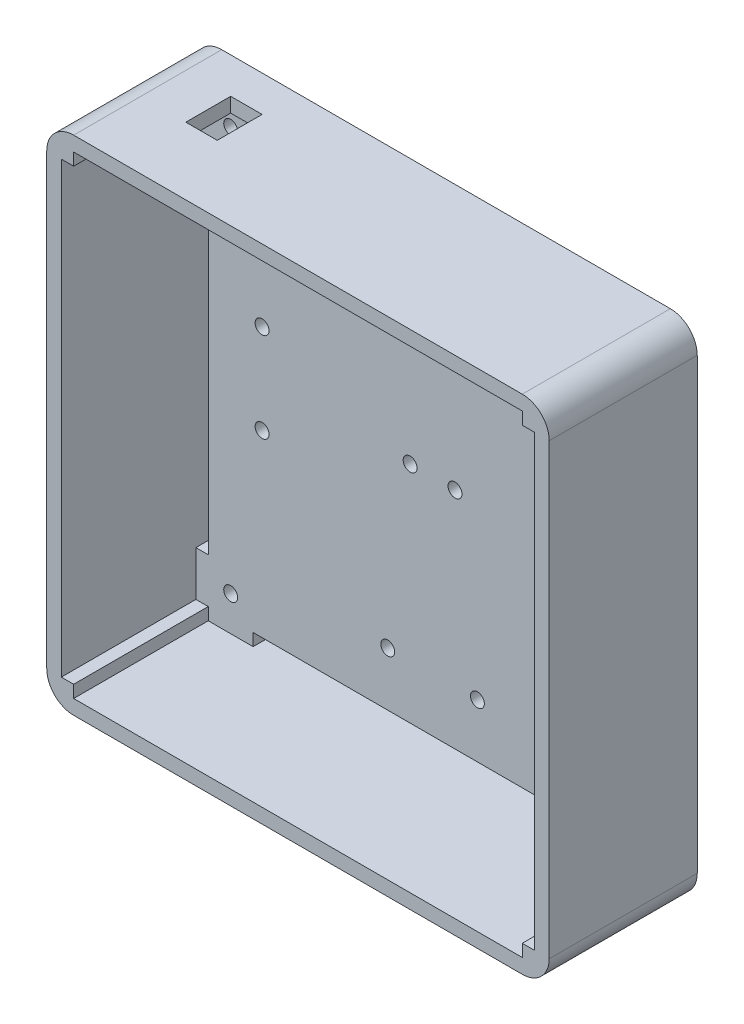
SolidWorks part; units mm, degrees
ref_plane "前视基准面" through (0, 0, 0) normal (0, 0, 1) x (1, 0, 0)
ref_plane "上视基准面" through (0, 0, 0) normal (0, 1, 0) x (1, 0, 0)
ref_plane "右视基准面" through (0, 0, 0) normal (1, 0, 0) x (0, 0, -1)
sketch "草图1" plane through (0, 0, 0) normal (0, 0, 1) x (1, 0, 0)
  line L0 (0, 0) -> (100, 0)
  line L5 (0, 0) -> (100, 0)
  line L6 (0, 0) -> (0, 100)
  line L7 (0, 100) -> (100, 100)
  line L9 (0, 0) -> (100, 0)
  line L10 (0, 0) -> (0, -6)
  line L11 (0, -6) -> (100, -6)
  line L12 (100, 0) -> (100, -6)
  line L14 (100, 0) -> (100, 50)
  line L17 (0, 100) -> (102.75, 100)
  line L21 (0, 100) -> (-6, 100)
  line L22 (0, 100) -> (0, 0)
  line L23 (0, 0) -> (-6, 0)
  line L24 (-6, 100) -> (-6, 0)
  line L25 (-6, 100) -> (0, 100)
  line L34 (100, -6) -> (100, 0)
  line L38 (0, -6) -> (0, 0)
  line L39 (0, 0) -> (-6, 0)
  line L41 (100, 0) -> (0, 0)
  line L42 (100, 0) -> (95, 0)
  line L43 (95, 0) -> (95, 5)
  line L44 (100, 100) -> (95, 100)
  line L45 (95, 100) -> (95, 95)
  line L46 (0, 100) -> (100.25, 100)
  line L47 (0, 100) -> (100, 100)
  line L48 (0, 50) -> (43.45, 50)
  line L49 (56.55, 50) -> (100, 50)
  line L54 (46.55, 50) -> (53.45, 50)
  line L55 (100, 50) -> (96, 50)
  line L56 (96, 50) -> (96, 70)
  line L57 (96, 70) -> (96, 50)
  line L58 (96, 50) -> (96, 30)
  line L59 (88, 70) -> (88, 30)
  line L60 (96, 30) -> (93, 30)
  line L61 (96, 30) -> (96, 70)
  line L62 (96, 70) -> (93, 70)
  line L63 (93, 30) -> (93, 70)
  line L64 (93, 30) -> (83, 30)
  line L65 (93, 30) -> (93, 70)
  line L66 (93, 70) -> (83, 70)
  line L67 (83, 30) -> (83, 70)
  line L68 (88, 50) -> (88, 30)
  line L69 (88, 50) -> (88, 70)
  line L70 (50, 100) -> (50, 96)
  line L71 (50, 96) -> (30, 96)
  line L72 (50, 96) -> (70, 96)
  line L73 (30, 88) -> (70, 88)
  line L74 (30, 96) -> (70, 96)
  line L75 (30, 96) -> (30, 93)
  line L76 (30, 93) -> (70, 93)
  line L77 (70, 96) -> (70, 93)
  line L78 (30, 93) -> (70, 93)
  line L79 (30, 93) -> (30, 83)
  line L80 (30, 83) -> (70, 83)
  line L81 (70, 93) -> (70, 83)
  line L82 (50, 88) -> (30, 88)
  line L83 (50, 88) -> (70, 88)
  line L84 (0, 50) -> (4, 50)
  line L85 (4, 50) -> (4, 70)
  line L86 (4, 70) -> (4, 50)
  line L87 (4, 50) -> (4, 30) construction
  line L88 (12, 70) -> (12, 50)
  line L89 (4, 70) -> (7, 70)
  line L90 (4, 70) -> (4, 30)
  line L91 (4, 30) -> (7, 30)
  line L92 (7, 70) -> (7, 30)
  line L93 (7, 30) -> (17, 30)
  line L94 (7, 30) -> (7, 70)
  line L95 (7, 70) -> (17, 70)
  line L96 (17, 30) -> (17, 70)
  line L97 (12, 50) -> (12, 30)
  line L98 (50, 0) -> (50, 4)
  line L99 (50, 4) -> (30, 4)
  line L100 (30, 4) -> (50, 4)
  line L101 (50, 4) -> (70, 4)
  line L102 (70, 4) -> (70, 7)
  line L103 (70, 7) -> (30, 7)
  line L104 (30, 7) -> (30, 4)
  line L105 (30, 12) -> (70, 12)
  line L106 (30, 7) -> (70, 7)
  line L107 (30, 7) -> (30, 17)
  line L108 (30, 17) -> (70, 17)
  line L109 (70, 7) -> (70, 17)
  line L110 (70, 12) -> (50, 12)
  line L111 (30, 12) -> (50, 12)
  line L112 (100.25, 4.6189) -> (100.25, 4.6388)
  line L113 (0, 0) -> (-2.75, 0)
  line L114 (0, 0) -> (0, 100)
  line L115 (0, 100) -> (-2.75, 100)
  line L116 (-2.75, 0) -> (-2.75, 100)
  line L117 (0, 100) -> (102.75, 100)
  line L125 (0, 100) -> (100.25, 100)
  line L126 (0, 100) -> (0, 0)
  line L127 (0, 0) -> (100, 0)
  line L129 (0, 100) -> (106, 100)
  line L130 (0, 100) -> (0, 0)
  line L131 (0, 0) -> (100, 0)
  line L133 (100.25, 4.6388) -> (100.25, 4.6189)
  line L134 (100.25, 4.6388) -> (100.25, 4.6189)
  line L135 (0, 100) -> (0, 0)
  line L136 (0, 0) -> (100, 0)
  line L137 (100, 100) -> (100, 0)
  line L138 (0, 100) -> (5, 100)
  line L139 (5, 100) -> (5, 95)
  line L140 (0, 0) -> (5, 0)
  line L141 (5, 0) -> (5, 5)
  line L143 (106, 100) -> (100, 100)
  line L144 (106, 100) -> (106, 0)
  line L145 (106, 0) -> (100, 0)
  line L146 (100, 100) -> (100, 0)
  line L147 (0, 100) -> (100, 100)
  line L148 (0, 100) -> (0, 106)
  line L149 (0, 106) -> (100, 106)
  line L150 (100, 100) -> (100, 106)
  line L151 (-6, 100) -> (0, 100)
  line L154 (0, 100) -> (0, 106)
  line L155 (106, 100) -> (100, 100)
  line L158 (100, 100) -> (100, 106)
  line L160 (100, -6) -> (100, 0)
  line L161 (100, 0) -> (106, 0)
  line L163 (0, 100) -> (100, 100)
  line L164 (0, 100) -> (0, 102.75)
  line L165 (0, 102.75) -> (100, 102.75)
  line L166 (100, 100) -> (100, 102.75)
  line L167 (100, 100) -> (102.75, 100)
  line L168 (100, 100) -> (100, 0)
  line L169 (100, 0) -> (102.75, 0)
  line L170 (102.75, 100) -> (102.75, 0)
  line L171 (0, 0) -> (100, 0)
  line L172 (0, 0) -> (0, -2.75)
  line L173 (0, -2.75) -> (100, -2.75)
  line L174 (100, 0) -> (100, -2.75)
  line L175 (0, 102.75) -> (10, 102.75)
  line L176 (0, 102.75) -> (0, 100)
  line L177 (0, 100) -> (10, 100)
  line L178 (10, 102.75) -> (10, 100)
  line L179 (-2.75, 100) -> (0, 100)
  line L180 (-2.75, 100) -> (-2.75, 90)
  line L181 (-2.75, 90) -> (0, 90)
  line L182 (0, 100) -> (0, 90)
  line L183 (100, 102.75) -> (90, 102.75)
  line L184 (100, 102.75) -> (100, 100)
  line L185 (100, 100) -> (90, 100)
  line L186 (90, 102.75) -> (90, 100)
  line L187 (100, 100) -> (102.75, 100)
  line L188 (100, 100) -> (100, 90)
  line L189 (100, 90) -> (102.75, 90)
  line L190 (102.75, 100) -> (102.75, 90)
  line L191 (102.75, 0) -> (100, 0)
  line L192 (102.75, 0) -> (102.75, 10)
  line L193 (102.75, 10) -> (100, 10)
  line L194 (100, 0) -> (100, 10)
  line L195 (100, -2.75) -> (90, -2.75)
  line L196 (100, -2.75) -> (100, 0)
  line L197 (100, 0) -> (90, 0)
  line L198 (90, -2.75) -> (90, 0)
  line L199 (0, 0) -> (10, 0)
  line L200 (0, 0) -> (0, -2.75)
  line L201 (0, -2.75) -> (10, -2.75)
  line L202 (10, 0) -> (10, -2.75)
  line L203 (0, 0) -> (-2.75, 0)
  line L204 (0, 0) -> (0, 10)
  line L205 (0, 10) -> (-2.75, 10)
  line L206 (-2.75, 0) -> (-2.75, 10)
  circle A2 centre (95, 95) radius 1.55
  circle A3 centre (95, 5) radius 1.55
  circle A4 centre (45, 50) radius 1.55
  circle A5 centre (55, 50) radius 1.55
  circle A6 centre (88, 40) radius 1.55
  circle A7 centre (88, 60) radius 1.55
  circle A8 centre (40, 88) radius 1.55
  circle A9 centre (60, 88) radius 1.55
  circle A10 centre (12, 60) radius 1.55
  circle A11 centre (12, 40) radius 1.55
  circle A12 centre (60, 12) radius 1.55
  circle A13 centre (40, 12) radius 1.55
  circle A14 centre (5, 95) radius 1.55
  circle A15 centre (5, 5) radius 1.55
  arc A16 (0, -6) -> (-6, 0) centre (0, 0) cw
  arc A17 (-6, 100) -> (0, 106) centre (0, 100) cw
  arc A18 (106, 100) -> (100, 106) centre (100, 100) ccw
  arc A19 (100, -6) -> (106, 0) centre (100, 0) ccw
  point P40 (50, 50)
extrude "凸台-拉伸4" add sketch "草图1" along normal blind 3 contours A15 L136 L171 L99 L104 L107 L108 L109 L102 L101 L41 A3 L14 L168 L49 L58 L60 L64 L67 A5 L54 A4 L48 L96 L93 L91 L90 L135 L6 L0 | A14 L7 L135 L22 L48 L85 L89 L95 L96 A4 L54 A5 L49 L67 L66 L62 L56 L168 L137 L17 A2 L163 L47 L72 L77 L81 L80 L79 L75 L71 L129 | A10 L88 L48 L96 L95 | A11 L97 L93 L96 L48 | A11 L97 L48 L92 L93 | A10 L88 L95 L92 L48 | L92 L89 L85 L48 | L92 L48 L90 L91 | A9 L73 A8 L79 L80 L81 | A9 L73 L81 L76 L79 A8 | L77 L72 L71 L75 L76 | A7 L59 L66 L67 L49 | A7 L59 L49 L63 L66 | L63 L49 L56 L62 | A6 L59 L64 L63 L49 | A6 L59 L49 L67 L64 | L63 L60 L58 L49 | A13 L105 A12 L109 L108 L107 | A13 L105 L107 L103 L109 A12 | L103 L104 L99 L101 L102 | L202 L136 L0 L10 L173 | L6 L205 L116 L23 | L116 L181 L135 L21 | L178 L165 L148 L7 L129 | L165 L186 L163 L17 L150 | L137 L189 L170 L17 | L198 L173 L12 L41 L171 | L170 L193 L14 L161 | L59 L68 L69 region at (50, 5.5, 0) region at (50, 24.964, 0) region at (-1.375, 5, 0) region at (5, -1.375, 0) region at (50, 94.5, 0) region at (50, 75.036, 0) region at (-1.375, 95, 0) region at (5.5, 60, 0) region at (5.5, 40, 0) region at (95, -1.375, 0) region at (5, 101.375, 0) region at (9.4278, 60, 0) region at (9.4278, 40, 0) region at (14.5722, 60, 0) region at (14.5722, 40, 0) region at (101.375, 5, 0) region at (50, 9.4278, 0) region at (101.375, 95, 0) region at (95, 101.375, 0) region at (50, 14.5722, 0) region at (94.5, 40, 0) region at (94.5, 60, 0) region at (90.5722, 40, 0) region at (90.5722, 60, 0) region at (50, 90.5722, 0) region at (85.4278, 40, 0) region at (85.4278, 60, 0) region at (50, 85.4278, 0)
extrude "凸台-拉伸5" add sketch "草图1<8>" along normal blind 33 contours L173 L38 L11 L160 | L145 L161 L12 L160 | L129 L170 L145 L144 | L158 L150 L17 L129 | L154 L165 L158 L149 | L25 L21 L148 L154 | L39 L116 L25 L24 | L38 L10 L23 L39 region at (-2.5465, -2.5465, 0) region at (50, -4.375, 0) region at (-4.375, 50, 0) region at (102.5465, -2.5465, 0) region at (-2.5465, 102.5465, 0) region at (104.375, 50, 0) region at (50, 104.375, 0) region at (102.5465, 102.5465, 0)
sketch "草图1<8>" plane through (0, 0, 0) normal (0, 0, 1) x (1, 0, 0) same geometry as "草图1"
sketch "草图3" plane through (0, 102.75, 0) normal (0, -1, 0) x (1, 0, 0)
  line L0 (10, 3) -> (10, 8)
  line L1 (10, 8) -> (17, 8)
  line L2 (17, 8) -> (17, 18)
  line L3 (17, 18) -> (10, 18)
  line L4 (10, 18) -> (10, 8)
extrude "切除-拉伸1" cut sketch "草图3" against normal blind 6 contours L3 L4 L1 L2 region at (13.5, 102.75, 13)
